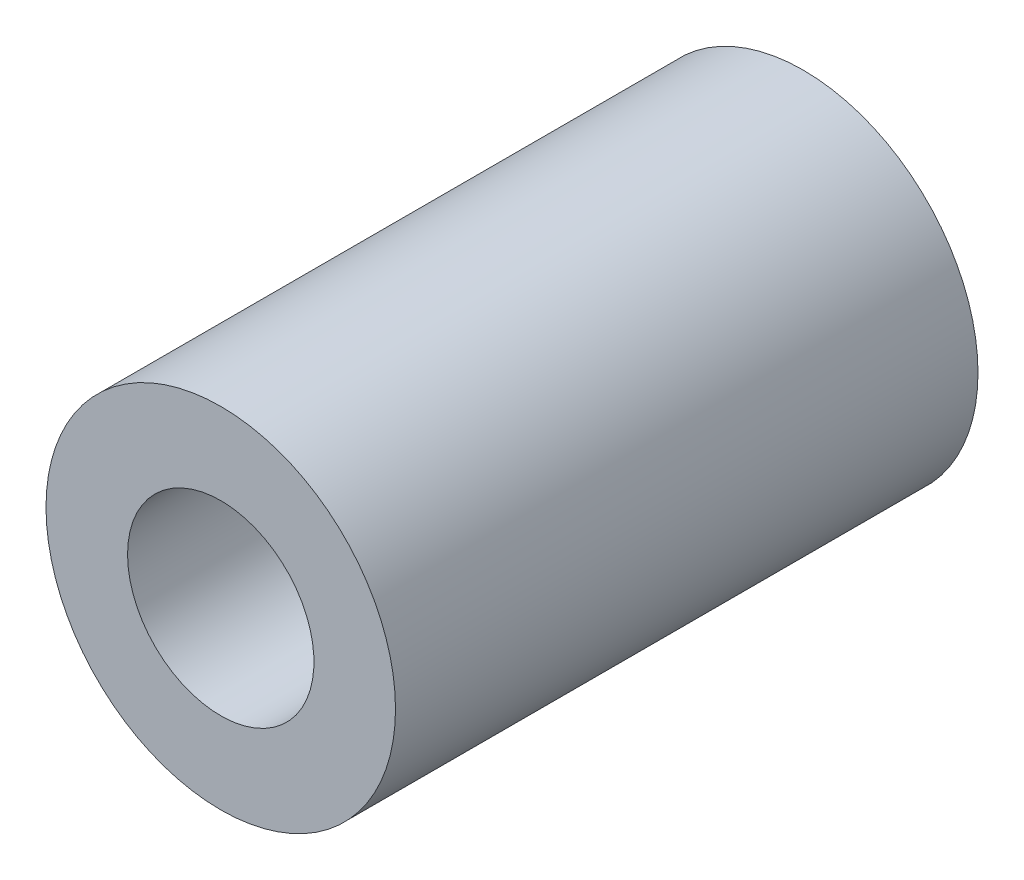
SolidWorks part; units mm, degrees
material "6061 合金"
ref_plane "正面" through (0, 0, 0) normal (0, 0, 1) x (1, 0, 0)
ref_plane "平面" through (0, 0, 0) normal (0, 1, 0) x (1, 0, 0)
ref_plane "右側面" through (0, 0, 0) normal (1, 0, 0) x (0, 0, -1)
sketch "断面" plane through (0, 0, 0) normal (0, 0, 1) x (1, 0, 0)
  circle A0 centre (0, 0) radius 3
  dimension "D1" = 6
extrude "軸全長" add sketch "断面" along normal blind 10
ref_axis "中心軸" through (0, 0, 10) along (0, 0, -1)
ref_plane "上面" through (0, 3, 0) normal (0, 1, 0) x (1, 0, 0)
sketch "上面穴スケッチ" plane through (0, 3, 0) normal (0, 1, 0) x (1, 0, 0)
  line L0 (0, -10) -> (0, 0) construction
  line L1 (3, 0) -> (-3, 0) construction
  circle A0 centre (0, -7) radius 1.6
  dimension "D1" = 7
  dimension "D2" = 3.2
extrude "上面穴貫通" [suppressed] cut sketch "上面穴スケッチ" against normal through all
sketch "上面キー溝スケッチ" plane through (0, 3, 0) normal (0, 1, 0) x (1, 0, 0)
  line L0 (0, -30) -> (0, -50) construction
  line L1 (0, -10) -> (0, 0) construction
  line L2 (1.5, -30) -> (1.5, -50)
  line L3 (-1.5, -30) -> (-1.5, -50)
  line L4 (3, 0) -> (-3, 0) construction
  arc A0 (1.5, -30) -> (-1.5, -30) centre (0, -30) ccw
  arc A1 (-1.5, -50) -> (1.5, -50) centre (0, -50) ccw
  point P5 (0, -40)
  dimension "D1" = 3
  dimension "D2" = 30
  dimension "D3" = 20
extrude "上面キー溝1.6mm" [suppressed] cut sketch "上面キー溝スケッチ" against normal blind 1.6
sketch "上面Dカットスケッチ" plane through (0, 3, 0) normal (0, 1, 0) x (1, 0, 0)
  line L0 (-3, 0) -> (-3, -10) construction
  line L1 (3, -10) -> (-3, -10)
  line L2 (3, -10) -> (3, 0)
  line L3 (3, 0) -> (-3, 0)
  line L4 (-3, -10) -> (-3, 0)
  dimension "D1" = 10
extrude "上面Dカット1mm" [suppressed] cut sketch "上面Dカットスケッチ" against normal blind 1
sketch "Eリング溝スケッチ" plane through (0, 0, 0) normal (0, 1, 0) x (1, 0, 0)
  line L0 (3, -10) -> (3, 0) construction
  line L1 (3, -1) -> (2, -1)
  line L2 (3, -1) -> (3, -2)
  line L3 (3, -2) -> (2, -2)
  line L4 (2, -1) -> (2, -2)
  line L5 (3, 0) -> (-3, 0) construction
  dimension "D1" = 1
  dimension "D2" = 1
revolve "Eリング溝カット" [suppressed] cut sketch "Eリング溝スケッチ" angle 360 about axis through (0, 0, 10) along (0, 0, -1)
sketch "ｽｹｯﾁ1" plane through (0, 0, 0) normal (0, 0, -1) x (-1, 0, 0)
  circle A0 centre (0, 0) radius 1.6
  dimension "D1" = 3.2
extrude "ｶｯﾄ - 押し出し1" cut sketch "ｽｹｯﾁ1" against normal through all
